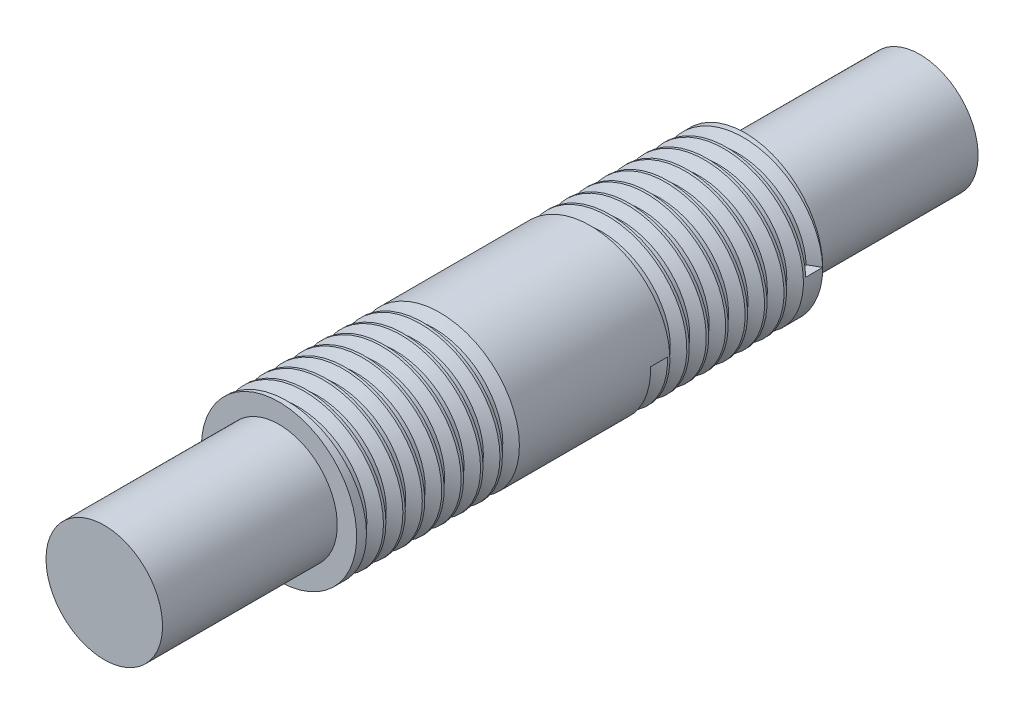
SolidWorks part; units mm, degrees
ref_plane "Front Plane" through (0, 0, 0) normal (0, 0, 1) x (1, 0, 0)
ref_plane "Top Plane" through (0, 0, 0) normal (0, 1, 0) x (1, 0, 0)
ref_plane "Right Plane" through (0, 0, 0) normal (1, 0, 0) x (0, 0, -1)
sketch "Sketch1" plane through (0, 0, 0) normal (0, 0, 1) x (1, 0, 0)
  circle A0 centre (0, 0) radius 4
  dimension "D1" = 8
extrude "Boss-Extrude1" add sketch "Sketch1" along normal mid plane 24
sketch "Sketch2" plane through (0, 0, 0) normal (0, 0, 1) x (1, 0, 0)
  circle A0 centre (0, 0) radius 3
  dimension "6" = 6
extrude "Boss-Extrude2" add sketch "Sketch2" along normal mid plane 42
thread "Thread1" pitch 1 method cut profile "Thread Profile1" start angle 0, offset 0, length 8, pitch 1, diameter 8
ref_plane "Plane1" through (-4, 0, 12) normal (0, -1, 0) x (-1, 0, 0)
sketch "Thread Profile1" plane through (-4, 0, 12) normal (0, -1, 0) x (-1, 0, 0)
  line L0 (0, 0) -> (0, 1) construction
  line L11 (0, 0) -> (0, 0.875)
  line L12 (0, 0.875) -> (-0.5413, 0.5625)
  line L13 (-0.5413, 0.5625) -> (-0.5413, 0.3125)
  line L15 (-0.5413, 0.3125) -> (0, 0)
  line L17 (-0.5413, 0.4375) -> (0, 0.4375) construction
  point P2 (0, 0)
  dimension "Pitch" = 1
  dimension "Profile_Angle" = 60
  dimension "Profile_Land" = 0.25
  dimension "Profile_Height" = 0.5413
thread "Thread2" pitch 1 method cut profile "Thread Profile2" start angle 0, offset 0, length 8, pitch 1, diameter 8
ref_plane "Plane2" through (4, 0, -12) normal (0, -1, 0) x (1, 0, 0)
sketch "Thread Profile2" plane through (4, 0, -12) normal (0, -1, 0) x (1, 0, 0)
  line L0 (0, 0) -> (0, 1) construction
  line L11 (0, 0) -> (0, 0.875)
  line L12 (0, 0.875) -> (-0.5413, 0.5625)
  line L13 (-0.5413, 0.5625) -> (-0.5413, 0.3125)
  line L15 (-0.5413, 0.3125) -> (0, 0)
  line L17 (-0.5413, 0.4375) -> (0, 0.4375) construction
  point P2 (0, 0)
  dimension "Pitch" = 1
  dimension "Profile_Angle" = 60
  dimension "Profile_Land" = 0.25
  dimension "Profile_Height" = 0.5413
